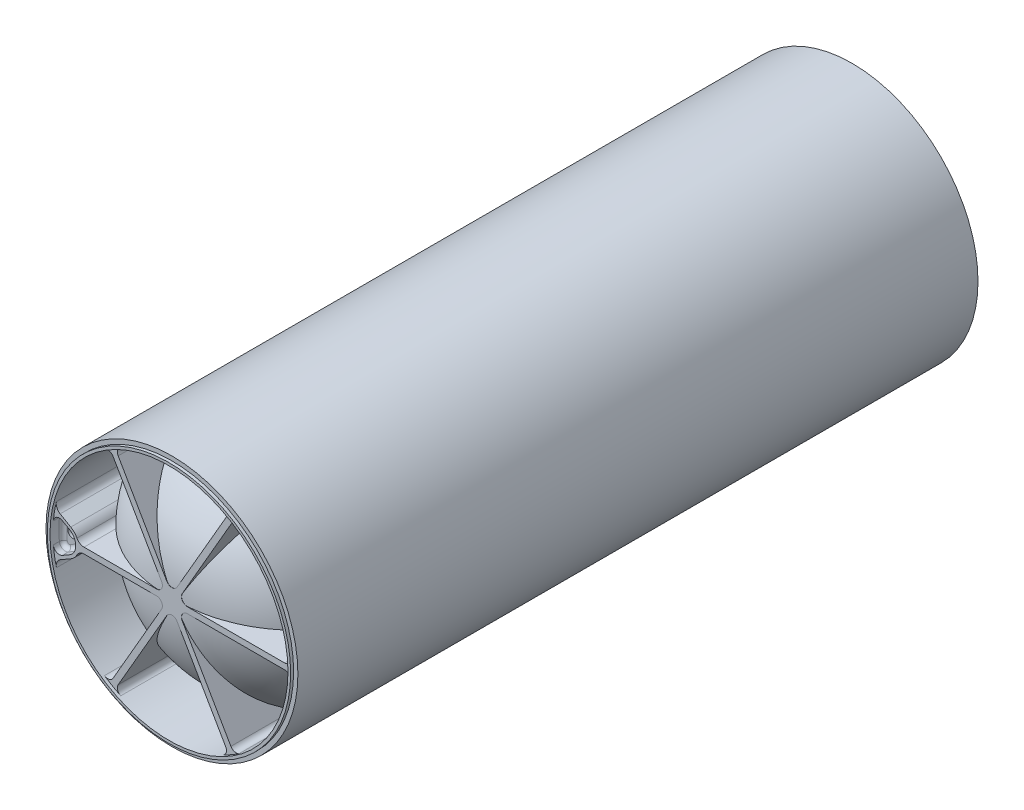
SolidWorks part; units mm, degrees
ref_plane "Front Plane" through (0, 0, 0) normal (0, 0, 1) x (1, 0, 0)
ref_plane "Top Plane" through (0, 0, 0) normal (0, 1, 0) x (1, 0, 0)
ref_plane "Right Plane" through (0, 0, 0) normal (1, 0, 0) x (0, 0, -1)
sketch "Sketch1" plane through (0, 0, 0) normal (0, 0, 1) x (1, 0, 0)
  circle A0 centre (-76.2, 0) radius 63.5
extrude "Boss-Extrude1" add sketch "Sketch1" along normal blind 342.9
fillet "Fillet1" radius 60 1 edges at (-12.7, 0, 342.9)
shell "Shell1" thickness 1.5875 removed face at (-12.7, 0, 0)
sketch "Sketch8" plane through (0, 0, 342.9) normal (0, 0, 1) x (1, 0, 0)
  line L0 (-76.2, 0) -> (12.7444, 0) construction
  line L1 (-76.1912, 0.0152) -> (24923.8088, 43301.2854) construction
  line L2 (-75.2371, -1.6677) -> (24924.7629, -43302.9379) construction
  line L3 (-131.2, 0) -> (24868.8, 43301.2702) construction
  line L4 (-130.6834, -0.8948) -> (24869.3166, -43302.165) construction
  line L5 (737.3254, -495.6699) -> (-43429.9702, 25004.3301) construction
  line L6 (-128.7, -4.3301) -> (43172.5702, 24995.6699) construction
  line L7 (-120.5346, -1.5) -> (-83.9942, -1.5)
  line L8 (-105.9101, 48.4594) -> (-81.3962, 6)
  line L9 (-103.312, -49.9594) -> (-78.7981, -7.5)
  line L10 (-120.5346, 1.5) -> (-83.9942, 1.5)
  line L11 (-103.312, 49.9594) -> (-78.7981, 7.5)
  line L12 (-105.9101, -48.4594) -> (-81.3962, -6)
  line L13 (-76.5362, -2.4177) -> (24923.4638, -43303.6879) construction
  line L14 (-73.9381, -0.9177) -> (24926.0619, -43302.1879) construction
  line L15 (-77.4903, 0.7652) -> (24922.5097, 43302.0354) construction
  line L16 (-74.8922, -0.7348) -> (24925.1078, 43300.5354) construction
  line L17 (-76.2, 1.5) -> (12.7444, 1.5) construction
  line L18 (-76.2, -1.5) -> (12.7444, -1.5) construction
  line L21 (-127.2, 6.9282) -> (-132.5527, 10.0186)
  line L22 (-132.5527, -10.0186) -> (-127.2, -6.9282)
  line L23 (-127.2, -6.9282) -> (43174.0702, 24993.0718) construction
  line L24 (738.8254, -493.0718) -> (-43428.4702, 25006.9282) construction
  line L25 (-73.6019, 7.5) -> (-49.088, 49.9594)
  line L26 (-68.4058, 1.5) -> (-19.3779, 1.5)
  line L27 (-71.0038, -6) -> (-46.4899, -48.4594)
  line L28 (-71.0038, 6) -> (-46.4899, 48.4594)
  line L29 (-68.4058, -1.5) -> (-19.3779, -1.5)
  line L30 (-73.6019, -7.5) -> (-49.088, -49.9594)
  circle A0 centre (-76.2, 0) radius 63.5 construction
  circle A1 centre (-76.2, 0) radius 63.5
  arc A2 (-110.2086, 49.4309) -> (-134.435, 14.4457) centre (-76.2, 0) ccw
  circle A3 centre (-76.2, 0) radius 55 construction
  circle A4 centre (-131.2, 0) radius 5 construction
  arc A5 (-50.3959, 54.1678) -> (-102.0041, 54.1678) centre (-76.2, 0) ccw
  arc A6 (-16.3873, 4.7368) -> (-42.1914, 49.4309) centre (-76.2, 0) ccw
  arc A7 (-42.1914, -49.4309) -> (-16.3873, -4.7368) centre (-76.2, 0) ccw
  arc A8 (-102.0041, -54.1678) -> (-50.3959, -54.1678) centre (-76.2, 0) ccw
  arc A9 (-134.435, -14.4457) -> (-110.2086, -49.4309) centre (-76.2, 0) ccw
  arc A11 (-124.0898, 3.6667) -> (-127.2, 6.9282) centre (-131.2, 0) ccw
  arc A13 (-127.2, -6.9282) -> (-124.0898, -3.6667) centre (-131.2, 0) ccw
  arc A14 (-134.435, -14.4457) -> (-132.5527, -10.0186) centre (-130.5527, -13.4827) cw
  arc A15 (-120.5346, -1.5) -> (-124.0898, -3.6667) centre (-120.5346, -5.5) ccw
  arc A16 (-120.5346, 1.5) -> (-124.0898, 3.6667) centre (-120.5346, 5.5) cw
  arc A17 (-132.5527, 10.0186) -> (-134.435, 14.4457) centre (-130.5527, 13.4827) cw
  arc A18 (-110.2086, -49.4309) -> (-105.9101, -48.4594) centre (-108.5082, -46.9594) ccw
  arc A19 (-102.0041, -54.1678) -> (-103.312, -49.9594) centre (-100.7139, -51.4594) cw
  arc A20 (-50.3959, -54.1678) -> (-49.088, -49.9594) centre (-51.6861, -51.4594) ccw
  arc A21 (-42.1914, -49.4309) -> (-46.4899, -48.4594) centre (-43.8918, -46.9594) cw
  arc A22 (-16.3873, -4.7368) -> (-19.3779, -1.5) centre (-19.3779, -4.5) ccw
  arc A23 (-19.3779, 1.5) -> (-16.3873, 4.7368) centre (-19.3779, 4.5) ccw
  arc A24 (-42.1914, 49.4309) -> (-46.4899, 48.4594) centre (-43.8918, 46.9594) ccw
  arc A25 (-49.088, 49.9594) -> (-50.3959, 54.1678) centre (-51.6861, 51.4594) ccw
  arc A26 (-103.312, 49.9594) -> (-102.0041, 54.1678) centre (-100.7139, 51.4594) cw
  arc A27 (-105.9101, 48.4594) -> (-110.2086, 49.4309) centre (-108.5082, 46.9594) ccw
  arc A30 (-83.9942, -1.5) -> (-81.3962, -6) centre (-83.9942, -4.5) cw
  arc A31 (-78.7981, -7.5) -> (-73.6019, -7.5) centre (-76.2, -9) cw
  arc A32 (-71.0038, -6) -> (-68.4058, -1.5) centre (-68.4058, -4.5) cw
  arc A33 (-68.4058, 1.5) -> (-71.0038, 6) centre (-68.4058, 4.5) cw
  arc A34 (-73.6019, 7.5) -> (-78.7981, 7.5) centre (-76.2, 9) cw
  arc A35 (-83.9942, 1.5) -> (-81.3962, 6) centre (-83.9942, 4.5) ccw
  dimension "D1" = 1.5
  dimension "D3" = 3
  dimension "D5" = 4
  dimension "D6" = 3
  dimension "D7" = 3
  dimension "D2" = 1.5
  dimension "D4" = 3
extrude "Boss-Extrude6" add sketch "Sketch8" against normal up to body
sketch "Sketch9" plane through (0, 0, 342.9) normal (0, 0, 1) x (1, 0, 0)
  circle A0 centre (-76.2, 0) radius 60
  circle A1 centre (-76.2, 0) radius 61.35
extrude "Boss-Extrude7" add sketch "Sketch9" along normal blind 1.5
sketch "Sketch11" plane through (0, 0, 342.9) normal (0, 0, 1) x (1, 0, 0)
  line L0 (-249.2763, -302.8263) -> (-160.332, -302.8263) construction
  line L2 (-248.3135, -304.494) -> (24751.6865, -43605.7642) construction
  line L4 (-303.7597, -303.7211) -> (24696.2403, -43604.9913) construction
  line L5 (564.2491, -798.4961) -> (-43603.0465, 24701.5039) construction
  line L6 (-301.7763, -307.1564) -> (42999.4939, 24692.8436) construction
  line L13 (-127.957, 5.6171) -> (-131.5229, 7.602)
  line L14 (-127.2038, -5.1088) -> (-131.482, -7.5788)
  circle A3 centre (-131.2, 0) radius 5 construction
  arc A9 (-135.9705, 5.2428) -> (-135.9705, -5.2428) centre (-76.2, 0) ccw
  arc A11 (-127.2038, -5.1088) -> (-127.957, 5.6171) centre (-131.2, 0) ccw
  arc A27 (-131.482, -7.5788) -> (-135.9705, -5.2428) centre (-132.982, -4.9807) cw
  arc A28 (-131.5229, 7.602) -> (-135.9705, 5.2428) centre (-132.982, 4.9807) ccw
extrude "Cut-Extrude1" cut sketch "Sketch11" against normal blind 5 contours A11 L13 A28 A9 A27 L14
sketch "Sketch12" plane through (0, 0, 337.9) normal (0, 0, 1) x (1, 0, 0)
  circle A0 centre (-131.2, 0) radius 2.5
extrude "Cut-Extrude2" cut sketch "Sketch12" against normal blind 30
sketch "Sketch13" plane through (0, 0, 0) normal (0, 0, -1) x (-1, 0, 0)
  circle A0 centre (131.2, 0) radius 2.5 construction
  circle A1 centre (131.2, 0) radius 2.5 construction
  circle A2 centre (131.2, 0) radius 5
extrude "Cut-Extrude3" cut sketch "Sketch13" against normal blind 327.56
fillet "Fillet2" radius 2 7 edges at (-136.2, 0, 327.56) (-129.7399, 6.6095, 337.9) (-134.3878, 7.6309, 337.9) (-136.2, 0, 337.9) (-134.3669, -7.6419, 337.9) (-124.7299, 0.4543, 337.9) (-129.3429, -6.3438, 337.9)
